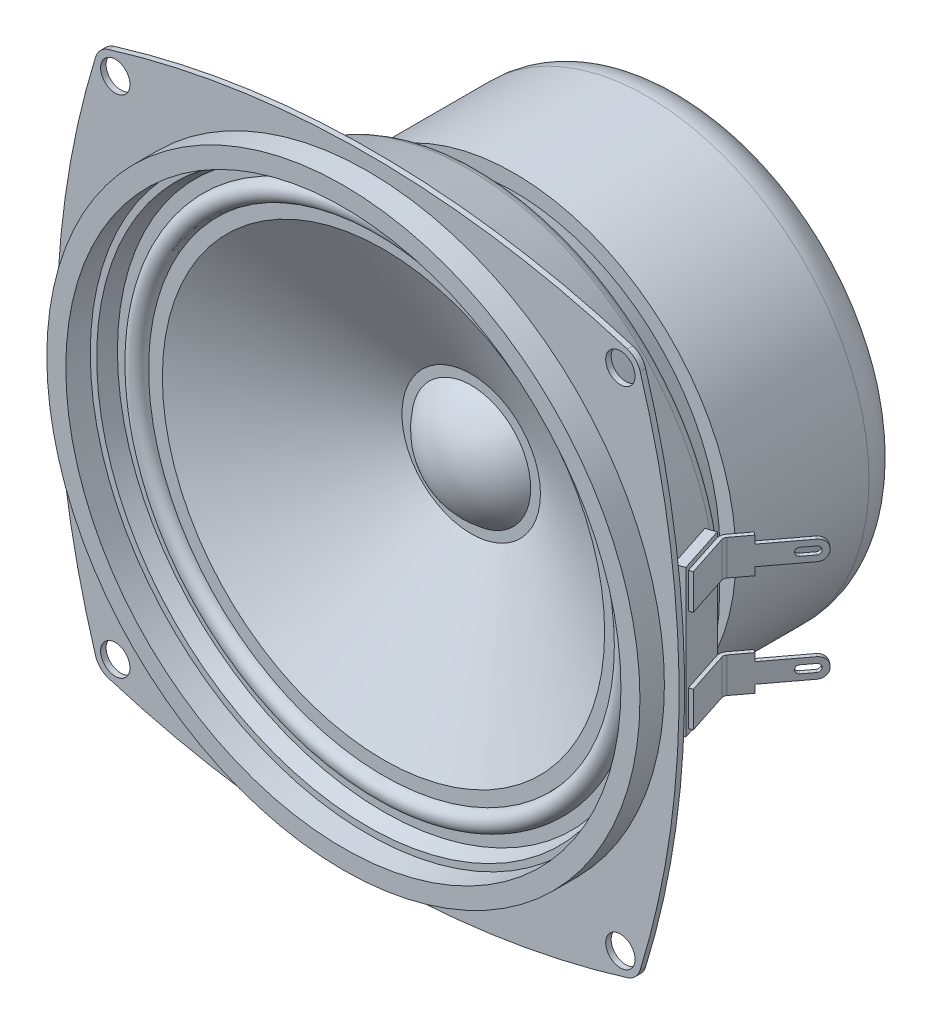
SolidWorks part; units mm, degrees
ref_plane "Front" through (0, 0, 0) normal (0, 0, 1) x (1, 0, 0)
ref_plane "Top" through (0, 0, 0) normal (0, 1, 0) x (1, 0, 0)
ref_plane "Right" through (0, 0, 0) normal (1, 0, 0) x (0, 0, -1)
sketch "Sketch3" plane through (0, 0, 0) normal (0, 0, 1) x (1, 0, 0)
  circle A0 centre (0, 0) radius 28.7528
  dimension "D1" = 57.5056
extrude "Extrude1" add sketch "Sketch3" along normal blind 22.352
fillet "Fillet1" radius 5.08 1 edges at (28.7528, 0, 0)
sketch "Sketch4" plane through (0, 0, 22.352) normal (0, 0, 1) x (1, 0, 0)
  circle A0 centre (0, 0) radius 26.67
  circle A1 centre (0, 0) radius 28.7528 construction
  dimension "D1" = 53.34
extrude "Extrude2" add sketch "Sketch4" along normal blind 4.318 draft 20 draft outward yes
sketch "Sketch5" plane through (0, 0, 26.67) normal (0, 0, 1) x (1, 0, 0)
  circle A0 centre (0, 0) radius 31.75
  dimension "D1" = 63.5
extrude "Extrude3" add sketch "Sketch5" along normal blind 13.97 draft 18 draft outward yes
sketch "Sketch7" plane through (0, 0, 40.64) normal (0, 0, 1) x (1, 0, 0)
  arc A0 (33.646, 35.3267) -> (-33.646, 35.3267) centre (0, -74.0233) ccw
  arc A1 (-35.3267, 33.646) -> (-35.3267, -33.646) centre (74.0233, 0) ccw
  arc A2 (-33.646, -35.3267) -> (33.646, -35.3267) centre (0, 74.0233) ccw
  arc A3 (35.3267, -33.646) -> (35.3267, 33.646) centre (-74.0233, 0) ccw
  arc A4 (-33.646, 35.3267) -> (-35.3267, 33.646) centre (-32.8991, 32.8991) ccw
  arc A5 (33.646, 35.3267) -> (35.3267, 33.646) centre (32.8991, 32.8991) cw
  arc A6 (35.3267, -33.646) -> (33.646, -35.3267) centre (32.8991, -32.8991) cw
  arc A7 (-33.646, -35.3267) -> (-35.3267, -33.646) centre (-32.8991, -32.8991) cw
  point P11 (-34.925, 34.925)
  point P14 (34.925, 34.925)
  point P18 (34.925, -34.925)
  point P21 (-34.925, -34.925)
  dimension "D1" = 34.925
  dimension "D6" = 114.4093
  dimension "D5" = 114.4093
  dimension "D7" = 114.4093
  dimension "D8" = 114.4093
  dimension "D9" = 2.54
  dimension "D2" = 69.85
  dimension "D3" = 69.85
  dimension "D4" = 34.925
extrude "Extrude4" add sketch "Sketch7" along normal blind 0.7112
sketch "Sketch8" plane through (0, 0, 41.3512) normal (0, 0, 1) x (1, 0, 0)
  circle A0 centre (0, 0) radius 38.481
  circle A1 centre (0, 0) radius 36.0172
  dimension "D1" = 76.962
  dimension "D2" = 72.0344
extrude "Extrude5" add sketch "Sketch8" along normal blind 3.175
sketch "Sketch9" plane through (0, 0, 0) normal (0, 0, -1) x (-1, 0, 0)
  circle A0 centre (0, 0) radius 9.3345
  dimension "D1" = 18.669
extrude "Cut-Extrude1" cut sketch "Sketch9" against normal blind 1.016
fillet "Fillet2" radius 1.016 1 edges at (-9.3345, 0, 0)
sketch "Sketch10" plane through (0, 0, 40.64) normal (0, 0, -1) x (-1, 0, 0)
  circle A0 centre (-32.766, 32.766) radius 1.905
  circle A1 centre (32.766, 32.766) radius 1.905
  circle A2 centre (32.766, -32.766) radius 1.905
  circle A3 centre (-32.766, -32.766) radius 1.905
  dimension "D1" = 3.81
  dimension "D2" = 65.532
  dimension "D3" = 65.532
  dimension "D4" = 32.766
  dimension "D5" = 32.766
extrude "Cut-Extrude2" cut sketch "Sketch10" against normal through all
fillet "Fillet3" radius 2.54 1 edges at (31.75, 0, 26.67)
sketch "Sketch11" plane through (0, 0, 0) normal (0, 1, 0) x (1, 0, 0)
  line L0 (-33.646, -41.3512) -> (33.646, -41.3512) construction
  line L1 (0, -41.3512) -> (35.1849, -41.3512)
  line L2 (35.1849, -41.3512) -> (34.5246, -39.3192)
  line L3 (8.9836, -27.94) -> (7.7136, -27.94)
  line L4 (8.9836, -27.94) -> (28.693, -39.3192)
  line L5 (36.2891, -40.64) -> (32.3203, -28.4251) construction
  line L7 (-26.67, -22.352) -> (26.67, -22.352) construction
  line L8 (0, -54.3692) -> (0, 9.6673) construction
  line L9 (0, -31.877) -> (0, -41.3512)
  line L11 (28.693, -39.3192) -> (30.48, -39.3192)
  line L12 (33.02, -39.3192) -> (34.5246, -39.3192)
  arc A0 (0, -31.877) -> (7.7136, -27.94) centre (0, -22.352) ccw
  arc A1 (30.48, -39.3192) -> (33.02, -39.3192) centre (31.75, -39.3192) ccw
  dimension "D2" = 19.05
  dimension "D9" = 1.27
  dimension "D1" = 1.27
  dimension "D3" = 5.588
  dimension "D4" = 22.352
  dimension "D5" = 1.27
  dimension "D6" = 30
  dimension "D7" = 2.032
  dimension "D8" = 31.75
revolve "Cut-Revolve1" cut sketch "Sketch11" angle 360 about L8
ref_plane "Plane1" through (34.3047, 0, 34.5325) normal (0.9511, 0, -0.309) x (0, -1, 0)
sketch "Sketch12" plane through (34.3047, 0, 34.5325) normal (0.9511, 0, -0.309) x (0, -1, 0)
  line L0 (0, 93.4431) -> (0, -6.5569) construction
  line L1 (-9.525, 4.0731) -> (9.525, 4.0731)
  line L2 (-9.525, 4.0731) -> (-9.525, -2.2769)
  line L3 (-9.525, -2.2769) -> (9.525, -2.2769)
  line L4 (9.525, 4.0731) -> (9.525, -2.2769)
  dimension "D1" = 19.05
  dimension "D2" = 6.35
  dimension "D3" = 9.525
  dimension "D4" = 45.72
extrude "Extrude6" add sketch "Sketch12" along normal blind 1.27
ref_plane "Plane2" through (0, 8.89, 0) normal (0, 1, 0) x (-1, 0, 0)
sketch "Sketch13" plane through (0, 8.89, 0) normal (0, 1, 0) x (-1, 0, 0)
  line L0 (-34.2539, 30.2663) -> (-36.2161, 36.3055) construction
  line L1 (-34.0969, 29.7832) -> (-36.0591, 35.8224)
  line L2 (-36.0591, 35.8224) -> (-36.5423, 35.6654)
  line L3 (-36.5423, 35.6654) -> (-34.6617, 29.8777)
  line L4 (-34.6617, 29.8777) -> (-40.617, 21.9748)
  line L5 (-40.617, 21.9748) -> (-40.2113, 21.669)
  line L6 (-40.2113, 21.669) -> (-34.0969, 29.7832)
  line L7 (-36.2161, 36.3055) -> (-35.0083, 36.698) construction
  dimension "D1" = 0.508
  dimension "D2" = 0.508
  dimension "D3" = 125
  dimension "D4" = 10.16
  dimension "D5" = 0.508
  dimension "D6" = 6.35
extrude "Extrude7" add sketch "Sketch13" against normal blind 4.572
mirror "Mirror1" about plane through (0, 0, 0) normal (0, 1, 0) of "Extrude7"
sketch "Sketch14" plane through (36.4681, 0, 27.4806) normal (0.7986, 0, 0.6018) x (0.6018, 0, -0.7986)
  line L1 (6.8941, 8.89) -> (-0.0909, 8.89)
  line L2 (6.8941, 8.89) -> (6.8941, 7.874)
  line L3 (6.8941, 7.874) -> (-0.0909, 7.874)
  line L4 (-0.0909, 8.89) -> (-0.0909, 7.874)
  line L5 (6.8941, 4.318) -> (-0.0909, 4.318)
  line L6 (6.8941, 4.318) -> (6.8941, 5.334)
  line L7 (6.8941, 5.334) -> (-0.0909, 5.334)
  line L8 (-0.0909, 4.318) -> (-0.0909, 5.334)
  line L9 (6.8941, -4.318) -> (-0.0909, -4.318)
  line L10 (6.8941, -4.318) -> (6.8941, -5.334)
  line L11 (6.8941, -5.334) -> (-0.0909, -5.334)
  line L12 (-0.0909, -4.318) -> (-0.0909, -5.334)
  line L13 (6.8941, -8.89) -> (-0.0909, -8.89)
  line L14 (6.8941, -8.89) -> (6.8941, -7.874)
  line L15 (6.8941, -7.874) -> (-0.0909, -7.874)
  line L16 (-0.0909, -8.89) -> (-0.0909, -7.874)
  dimension "D1" = 2.54
  dimension "D2" = 1.016
  dimension "D3" = 1.016
  dimension "D4" = 2.54
  dimension "D5" = 6.985
extrude "Cut-Extrude3" cut sketch "Sketch14" against normal blind 0.508
fillet "Fillet4" radius 1.2446 4 edges at (40.4142, -7.874, 21.8219) (40.4142, -5.334, 21.8219) (40.4142, 7.874, 21.8219) (40.4142, 5.334, 21.8219)
sketch "Sketch15" plane through (36.4681, 0, 27.4806) normal (0.7986, 0, 0.6018) x (0.6018, 0, -0.7986)
  line L32 (6.1321, 6.5786) -> (6.1321, 6.6294)
  line L33 (5.6495, 7.112) -> (-0.8529, 7.112)
  line L34 (-0.8529, 7.112) -> (-0.8529, 8.128)
  line L35 (-0.8529, 8.128) -> (-2.2394, 8.128)
  line L36 (-2.2394, 8.128) -> (-2.2394, 5.08)
  line L37 (-2.2394, 5.08) -> (-0.8529, 5.08)
  line L38 (-0.8529, 5.08) -> (-0.8529, 6.096)
  line L39 (-0.8529, 6.096) -> (5.6495, 6.096)
  line L40 (6.1321, 6.5786) -> (6.1321, 6.6294)
  line L41 (5.6495, 7.112) -> (4.0747, 7.112)
  line L47 (4.0747, 6.096) -> (5.6495, 6.096)
  line L64 (3.5921, 6.6294) -> (3.5921, 6.5786)
  arc A8 (6.1321, 6.6294) -> (5.6495, 7.112) centre (5.6495, 6.6294) ccw
  arc A9 (5.6495, 6.096) -> (6.1321, 6.5786) centre (5.6495, 6.5786) ccw
  arc A10 (6.1321, 6.6294) -> (5.6495, 7.112) centre (5.6495, 6.6294) ccw
  arc A11 (5.6495, 6.096) -> (6.1321, 6.5786) centre (5.6495, 6.5786) ccw
  arc A16 (4.0747, 7.112) -> (3.5921, 6.6294) centre (4.0747, 6.6294) ccw
  arc A17 (3.5921, 6.5786) -> (4.0747, 6.096) centre (4.0747, 6.5786) ccw
  dimension "D5" = 2.54
  dimension "D2" = 0.762
extrude "Cut-Extrude4" cut sketch "Sketch15" against normal blind 0.508
mirror "Mirror2" about plane through (0, 0, 0) normal (0, 1, 0) of "Cut-Extrude4"
fillet "Fillet5" radius 1.27 2 edges at (34.0969, 6.604, 29.7832) (34.0969, -6.604, 29.7832)
fillet "Fillet6" radius 0.635 2 edges at (34.6617, -6.604, 29.8777) (34.6617, 6.604, 29.8777)
